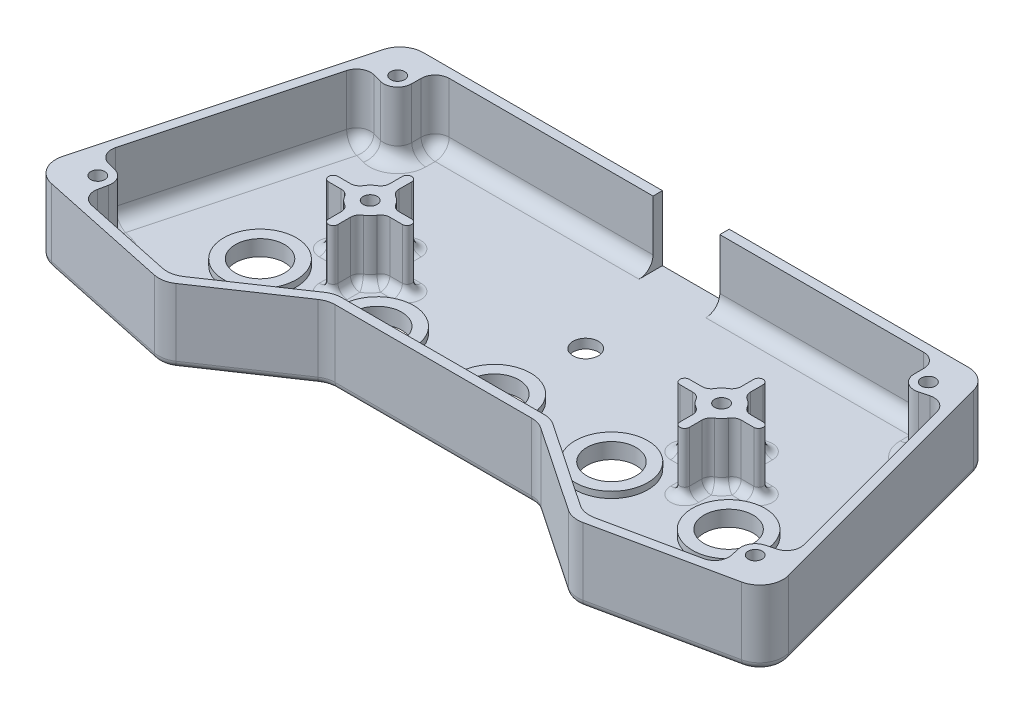
SolidWorks part; units mm, degrees
ref_plane "Front Plane" through (0, 0, 0) normal (0, 0, 1) x (1, 0, 0)
ref_plane "Top Plane" through (0, 0, 0) normal (0, 1, 0) x (1, 0, 0)
ref_plane "Right Plane" through (0, 0, 0) normal (1, 0, 0) x (0, 0, -1)
sketch "Sketch10" plane through (0, 0, 0) normal (0, 1, 0) x (1, 0, 0)
  line L0 (62, 32) -> (-62, 32)
  line L1 (-62, 32) -> (-78.8232, -30.7852)
  line L2 (-78.8232, -30.7852) -> (-43.6451, -38.2625)
  line L3 (-43.6451, -38.2625) -> (-22.5, -24)
  line L4 (-22.5, -24) -> (22.5, -24)
  line L5 (22.5, -24) -> (43.6451, -38.2625)
  line L6 (43.6451, -38.2625) -> (78.8232, -30.7852)
  line L7 (78.8232, -30.7852) -> (62, 32)
  line L8 (-50, -11) -> (-25, -11) construction
  line L9 (-25, -11) -> (0, -11) construction
  line L10 (0, -11) -> (25, -11) construction
  line L11 (25, -11) -> (50, -11) construction
  line L12 (-27, 0) -> (27, 0) construction
  line L13 (0, 0) -> (0, 32) construction
  line L14 (0, 0) -> (0, -24) construction
  line L15 (78.8232, -30.7852) -> (22.5, -24) construction
  line L16 (-22.5, -24) -> (-78.8232, -30.7852) construction
  circle A0 centre (50, -11) radius 5.25
  circle A2 centre (0, -11) radius 5.25
  circle A3 centre (25, -11) radius 5.25
  circle A5 centre (-50, -11) radius 5.25
  circle A6 centre (-25, -11) radius 5.25
  dimension "D1" = 10.5
  dimension "D2" = 25
  dimension "D3" = 65
  dimension "D4" = 124
  dimension "D5" = 11
  dimension "D6" = 105
  dimension "D7" = 56
  dimension "D8" = 45
  dimension "D9" = 32
  dimension "D10" = 34
  dimension "D11" = 12
extrude "Boss-Extrude5" add sketch "Sketch10" along normal blind 2 separate body
sketch "Sketch11" plane through (0, 2, 0) normal (0, 1, 0) x (1, 0, 0)
  line L0 (-78.8232, -30.7852) -> (-62, 32)
  line L1 (-62, 32) -> (62, 32)
  line L2 (62, 32) -> (78.8232, -30.7852)
  line L3 (78.8232, -30.7852) -> (43.6451, -38.2625)
  line L4 (43.6451, -38.2625) -> (22.5, -24)
  line L5 (22.5, -24) -> (-22.5, -24)
  line L6 (-22.5, -24) -> (-43.6451, -38.2625)
  line L7 (-43.6451, -38.2625) -> (-78.8232, -30.7852)
  line L8 (-44.0596, -36.1297) -> (-76.3459, -29.2671)
  line L9 (-76.3459, -29.2671) -> (-60.4653, 30)
  line L10 (-60.4653, 30) -> (60.4653, 30)
  line L11 (60.4653, 30) -> (76.3459, -29.2671)
  line L12 (76.3459, -29.2671) -> (44.0596, -36.1297)
  line L13 (44.0596, -36.1297) -> (23.1115, -22)
  line L14 (23.1115, -22) -> (-23.1115, -22)
  line L15 (-23.1115, -22) -> (-44.0596, -36.1297)
  dimension "D1" = 2
extrude "Boss-Extrude7" add sketch "Sketch11" along direction (0, -1, 0) on the side of the normal offset from surface (13.875 mm away) 15.875 up to face at (-50, 0, 16.25)
fillet "Fillet4" radius 5 16 edges at (62, 7.9375, -32) (78.8232, 7.9375, 30.7852) (43.6451, 7.9375, 38.2625) (22.5, 7.9375, 24) (-22.5, 7.9375, 24) (-43.6451, 7.9375, 38.2625) (-62, 7.9375, -32) (-78.8232, 7.9375, 30.7852) (76.3459, 8.9375, 29.2671) (60.4653, 8.9375, -30) (44.0596, 8.9375, 36.1297) (23.1115, 8.9375, 22) (-23.1115, 8.9375, 22) (-44.0596, 8.9375, 36.1297) (-76.3459, 8.9375, 29.2671) (-60.4653, 8.9375, -30)
fillet "Fillet5" radius 1.5 16 edges at (43.7275, 0, 37.8387) (32.8264, 0, 30.9653) (22.4332, 0, 24.2185) (0, 0, 24) (-22.4332, 0, 24.2185) (-32.8264, 0, 30.9653) (-43.7275, 0, 37.8387) (-59.6953, 0, 34.851) (-76.8931, 0, 29.6024) (-70.2263, 0, -1.2991) (-61.2072, 0, -30.9668) (0, 0, -32) (61.2072, 0, -30.9668) (70.2263, 0, -1.2991) (76.8931, 0, 29.6024) (59.6953, 0, 34.851)
sketch "Sketch12" plane through (0, 2, 0) normal (0, 1, 0) x (1, 0, 0)
  line L0 (-62.2348, 23.3963) -> (-57.4052, 22.1022)
  line L1 (-61.4583, 26.2941) -> (-74.9822, -24.1777) construction
  line L2 (-53.6287, 25) -> (-53.6287, 30)
  line L3 (56.6287, 30) -> (-56.6287, 30) construction
  line L4 (-53.6287, 30) -> (-56.6287, 30)
  line L5 (-61.4583, 26.2941) -> (-62.2348, 23.3963)
  line L6 (-74.9822, -24.1777) -> (-74.2058, -21.2799)
  line L7 (-74.2058, -21.2799) -> (-69.3761, -22.574)
  line L8 (-67.2181, -26.0955) -> (-68.2577, -30.9863)
  line L9 (-71.1921, -30.3625) -> (-46.1356, -35.6885) construction
  line L10 (-68.2577, -30.9863) -> (-71.1921, -30.3625)
  line L11 (0, 0) -> (0, 17.9434) construction
  line L12 (68.2577, -30.9863) -> (71.1921, -30.3625)
  line L13 (67.2181, -26.0955) -> (68.2577, -30.9863)
  line L14 (74.2058, -21.2799) -> (69.3761, -22.574)
  line L15 (74.9822, -24.1777) -> (74.2058, -21.2799)
  line L16 (61.4583, 26.2941) -> (62.2348, 23.3963)
  line L17 (53.6287, 30) -> (56.6287, 30)
  line L18 (53.6287, 25) -> (53.6287, 30)
  line L19 (62.2348, 23.3963) -> (57.4052, 22.1022)
  arc A0 (-57.4052, 22.1022) -> (-53.6287, 25) centre (-56.6287, 25) ccw
  arc A1 (-56.6287, 30) -> (-61.4583, 26.2941) centre (-56.6287, 25) ccw
  arc A2 (-69.3761, -22.574) -> (-67.2181, -26.0955) centre (-70.1526, -25.4718) cw
  arc A3 (-71.1921, -30.3625) -> (-74.9822, -24.1777) centre (-70.1526, -25.4718) cw
  circle A4 centre (-56.6287, 25) radius 1.5
  circle A5 centre (-70.1526, -25.4718) radius 1.5
  circle A6 centre (70.1526, -25.4718) radius 1.5
  circle A7 centre (56.6287, 25) radius 1.5
  arc A8 (71.1921, -30.3625) -> (74.9822, -24.1777) centre (70.1526, -25.4718) ccw
  arc A9 (69.3761, -22.574) -> (67.2181, -26.0955) centre (70.1526, -25.4718) ccw
  arc A10 (56.6287, 30) -> (61.4583, 26.2941) centre (56.6287, 25) cw
  arc A11 (57.4052, 22.1022) -> (53.6287, 25) centre (56.6287, 25) cw
  dimension "D1" = 3
  dimension "D2" = 1.5
extrude "Boss-Extrude8" add sketch "Sketch12" along normal up to surface (13.875 mm away) up to face at (0, 15.875, 14.2385)
sketch "Sketch14" plane through (0, 0, -30) normal (0, 0, 1) x (1, 0, 0)
  line L0 (-53.6287, 15.875) -> (53.6287, 15.875) construction
  line L5 (0, 0) -> (0, 15.875) construction
  line L10 (-6.625, 15.03) -> (-6.625, 2.5) construction
  line L11 (-7.125, 15.875) -> (7.125, 15.875)
  line L12 (-7.125, 15.875) -> (-7.125, 2)
  line L13 (-7.125, 2) -> (7.125, 2)
  line L14 (7.125, 15.875) -> (7.125, 2)
  line L15 (53.6287, 2) -> (-53.6287, 2) construction
  dimension "D1" = 0.5
extrude "Cut-Extrude2" cut sketch "Sketch14" against normal through all
sketch "Sketch15" plane through (0, 0, 0) normal (0, -1, 0) x (1, 0, 0)
  line L0 (0, -8.5) -> (0, -30.5) construction
  line L1 (-58.1634, -30.5) -> (58.1634, -30.5) construction
  circle A0 centre (0, -8.5) radius 2.7
  dimension "D2" = 5.4
  dimension "D1" = 22
extrude "Cut-Extrude3" cut sketch "Sketch15" against normal through all contours A0
sketch "Sketch16" plane through (0, 2, 0) normal (0, 1, 0) x (1, 0, 0)
  circle A0 centre (25, -11) radius 7.75
  circle A1 centre (25, -11) radius 5.25
  circle A2 centre (0, -11) radius 7.75
  circle A3 centre (0, -11) radius 5.25
  circle A4 centre (-50, -11) radius 5.25
  circle A5 centre (-50, -11) radius 7.75
  circle A6 centre (-25, -11) radius 5.25
  circle A7 centre (-25, -11) radius 7.75
  circle A9 centre (-50, -11) radius 5.25 construction
  circle A10 centre (-25, -11) radius 5.25 construction
  circle A12 centre (25, -11) radius 5.25 construction
  circle A13 centre (0, -11) radius 5.25 construction
  circle A14 centre (50, -11) radius 7.75
  circle A15 centre (50, -11) radius 5.25
  circle A16 centre (50, -11) radius 5.25 construction
  dimension "D1" = 2.5
extrude "Boss-Extrude9" add sketch "Sketch16" along normal blind 1.35
sketch "Sketch17" plane through (0, 2, 0) normal (0, 1, 0) x (1, 0, 0)
  line L0 (-38.5, 3.873) -> (-38.5, 7.873)
  line L3 (-36.5, 7.873) -> (-36.5, 3.873)
  line L4 (-33.627, 1) -> (-29.627, 1)
  line L5 (-29.627, -1) -> (-33.627, -1)
  line L8 (-41.373, -1) -> (-45.373, -1)
  line L9 (-45.373, 1) -> (-41.373, 1)
  line L10 (-45.373, 0) -> (-37.5, 0) construction
  line L11 (-37.5, 0) -> (-29.627, 0) construction
  line L12 (-37.5, -1.5) -> (-37.5, 0) construction
  line L13 (-37.5, 7.873) -> (-37.5, 0) construction
  line L14 (-38.5, -3.873) -> (-38.5, -7.873)
  line L15 (-37.5, 0) -> (0, 0) construction
  line L16 (-36.5, -7.873) -> (-36.5, -3.873)
  line L17 (-37.5, -7.873) -> (-37.5, 0) construction
  arc A0 (-38.5, 3.873) -> (-41.373, 1) centre (-37.5, 0) ccw
  arc A3 (-38.5, 7.873) -> (-36.5, 7.873) centre (-37.5, 7.873) cw
  arc A4 (-29.627, 1) -> (-29.627, -1) centre (-29.627, 0) cw
  arc A6 (-45.373, -1) -> (-45.373, 1) centre (-45.373, 0) cw
  arc A7 (-33.627, 1) -> (-36.5, 3.873) centre (-37.5, 0) ccw
  arc A8 (-41.373, -1) -> (-38.5, -3.873) centre (-37.5, 0) ccw
  circle A10 centre (-37.5, 0) radius 1.5
  arc A11 (-38.5, -7.873) -> (-36.5, -7.873) centre (-37.5, -7.873) ccw
  arc A12 (-36.5, -3.873) -> (-33.627, -1) centre (-37.5, 0) ccw
  dimension "D1" = 37.5
  dimension "D4" = 8
  dimension "D5" = 3
  dimension "D2" = 2
  dimension "D3" = 4
extrude "PCB Mount Posts" add sketch "Sketch17" along normal offset from surface (12.875 mm away) 1 up to face at (0, 15.875, 7.9916)
fillet "Fillet6" radius 2 8 edges at (-41.373, 8.4375, -1) (-38.5, 8.4375, -3.873) (-36.5, 8.4375, -3.873) (-33.627, 8.4375, -1) (-33.627, 8.4375, 1) (-36.5, 8.4375, 3.873) (-38.5, 8.4375, 3.873) (-41.373, 8.4375, 1)
mirror "Mirror1" about plane through (0, 0, 0) normal (1, 0, 0) of "Fillet6", "Boss-Extrude9", "PCB Mount Posts"
sketch "Sketch20" plane through (0, 0, 0) normal (0, -1, 0) x (1, 0, 0)
  line L0 (12.7379, 3) -> (-12.7379, 3) construction
  line L1 (0, 11) -> (0, 3) construction
  circle A0 centre (0, 11) radius 5.25 construction
  text T0 "RESET\r\n" font "Arial" height 5
  dimension "D1" = 8
extrude "Reset" cut sketch "Sketch20" against normal blind 0.5
sketch "Sketch21" plane through (0, 0, 0) normal (0, -1, 0) x (1, 0, 0)
  line L0 (27.3094, -4) -> (27.3094, 4)
  line L1 (27.3094, 4) -> (20.3812, 0)
  line L2 (20.3812, 0) -> (27.3094, -4)
  line L3 (-25, 11) -> (-25, 0) construction
  line L4 (-21.5, -4) -> (-23.5, -4)
  line L5 (-21.5, -4) -> (-21.5, 4)
  line L6 (-21.5, 4) -> (-23.5, 4)
  line L7 (-23.5, -4) -> (-23.5, 4)
  line L8 (-26.5, -4) -> (-28.5, -4)
  line L9 (-26.5, -4) -> (-26.5, 4)
  line L10 (-26.5, 4) -> (-28.5, 4)
  line L11 (-28.5, -4) -> (-28.5, 4)
  line L12 (-25, 0) -> (-26.5, 0) construction
  line L13 (-25, 0) -> (-23.5, 0) construction
  line L14 (20.3812, 0) -> (-21.5, 0) construction
  line L15 (27.3094, 0) -> (25, 0) construction
  line L16 (25, 0) -> (23.8453, -2) construction
  line L17 (25, 0) -> (23.8453, 2) construction
  line L18 (25, 11) -> (25, 0) construction
  line L22 (22.8812, 0) -> (26.0594, -1.8349)
  line L23 (26.0594, -1.8349) -> (26.0594, 1.8349)
  line L24 (26.0594, 1.8349) -> (22.8812, 0)
  circle A0 centre (-25, 11) radius 5.25 construction
  dimension "D1" = 3
  dimension "D2" = 11
  dimension "D3" = 8
  dimension "D4" = 2
  dimension "D5" = 1.25
extrude "Cut-Extrude4" cut sketch "Sketch21" against normal blind 0.5
fillet "Fillet7" radius 2 48 edges at (41.6962, 2, 1.2679) (44.0346, 2, 1) (46.373, 2, 0) (44.0346, 2, -1) (41.6962, 2, -1.2679) (40.3284, 2, -2.8284) (38.7679, 2, -4.1962) (38.5, 2, -6.5346) (37.5, 2, -8.873) (36.5, 2, -6.5346) (36.2321, 2, -4.1962) (34.6716, 2, -2.8284) (33.3038, 2, -1.2679) (30.9654, 2, -1) (28.627, 2, 0) (30.9654, 2, 1) (33.3038, 2, 1.2679) (34.6716, 2, 2.8284) (36.2321, 2, 4.1962) (36.5, 2, 6.5346) (37.5, 2, 8.873) (38.5, 2, 6.5346) (38.7679, 2, 4.1962) (-36.2321, 2, 4.1962) (-36.5, 2, 6.5346) (-37.5, 2, 8.873) (-38.5, 2, 6.5346) (-38.7679, 2, 4.1962) (-40.3284, 2, 2.8284) (-41.6962, 2, 1.2679) (-44.0346, 2, 1) (-46.373, 2, 0) (-44.0346, 2, -1) (-41.6962, 2, -1.2679) (-40.3284, 2, -2.8284) (-38.7679, 2, -4.1962) (-38.5, 2, -6.5346) (-37.5, 2, -8.873) (-36.5, 2, -6.5346) (-36.2321, 2, -4.1962) (-34.6716, 2, -2.8284) (-33.3038, 2, -1.2679) (-30.9654, 2, -1) (-28.627, 2, 0) (-30.9654, 2, 1) (-33.3038, 2, 1.2679) (40.3284, 2, 2.8284) (-34.6716, 2, 2.8284)
fillet "Fillet8" radius 3 8 edges at (-74.2058, 8.9375, 21.2799) (-68.2577, 8.9375, 30.9863) (68.2577, 8.9375, 30.9863) (74.2058, 8.9375, 21.2799) (62.2348, 8.9375, -23.3963) (53.6287, 8.9375, -30) (-53.6287, 8.9375, -30) (-62.2348, 8.9375, -23.3963)
fillet "Fillet9" radius 3 33 edges at (28.8769, 2, -30) (52.75, 2, -29.1213) (53.6287, 2, -26) (54.8024, 2, -22.6199) (58.3711, 2, -22.361) (61.6135, 2, -22.3202) (68.2203, 2, -1.0582) (73.1296, 2, 20.6586) (70.3421, 2, 22.3152) (67.5947, 2, 23.9043) (67.4261, 2, 27.0737) (67.2155, 2, 30.3095) (55.7295, 2, 33.6492) (44.142, 2, 35.7059) (33.3394, 2, 28.8989) (23.0447, 2, 22.2185) (0, 2, 22) (-23.0447, 2, 22.2185) (-33.3394, 2, 28.8989) (-44.142, 2, 35.7059) (-55.7295, 2, 33.6492) (-67.2155, 2, 30.3095) (-67.4261, 2, 27.0737) (-67.5947, 2, 23.9043) (-70.3421, 2, 22.3152) (-73.1296, 2, 20.6586) (-68.2203, 2, -1.0582) (-61.6135, 2, -22.3202) (-58.3711, 2, -22.361) (-54.8024, 2, -22.6199) (-53.6287, 2, -26) (-52.75, 2, -29.1213) (-28.8769, 2, -30)
equation "\"TextAngle\"= 65"
equation "\"TextFromCircle\"=8"
